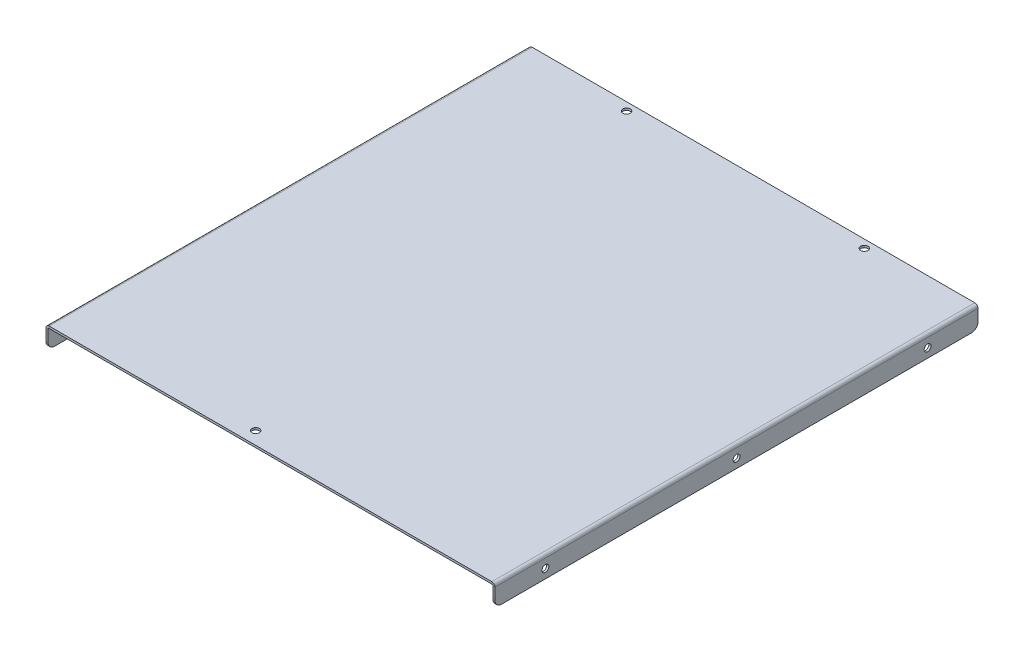
SolidWorks part; units mm, degrees
note: The reader was unsure of these and kept them because the rebuilt part matched: flange length of "Edge-Flange1", "Edge-Flange2".
ref_plane "Front Plane" through (0, 0, 0) normal (0, 0, 1) x (1, 0, 0)
ref_plane "Top Plane" through (0, 0, 0) normal (0, 1, 0) x (1, 0, 0)
ref_plane "Right Plane" through (0, 0, 0) normal (1, 0, 0) x (0, 0, -1)
sketch "Sketch1" plane through (0, 0, 0) normal (0, 1, 0) x (1, 0, 0)
  line L1 (-105.75, 113.75) -> (105.75, 113.75)
  line L2 (-105.75, 113.75) -> (-105.75, -113.75)
  line L3 (-105.75, -113.75) -> (105.75, -113.75)
  line L4 (105.75, 113.75) -> (105.75, -113.75)
  line L5 (-105.75, 113.75) -> (105.75, -113.75) construction
  line L6 (-105.75, -113.75) -> (105.75, 113.75) construction
  point P0 (0, 0)
  dimension "D1" = 211.5
  dimension "D2" = 227.5
base flange "Base-Flange1" sketch "Sketch1" thickness 1 reverse thickness direction no parameters "D1"=8
ref_plane "Plane1" through (105.75, -1, 113.75) normal (0, 0, -1) x (-1, 0, 0)
edge flange "Edge-Flange1" sketch "Sketch9" flange angle 90 flange length 10 flange position material inside bend radius 0.5 thickness 1 relief rectangular parameters "D6"=10
sketch "Sketch9" plane through (105.75, -1, 0) normal (1, 0, 0) x (0, 0, 1)
  line L2 (-113.75, 0) -> (-113.75, 9)
  line L3 (-113.75, 9) -> (113.75, 9)
  line L4 (113.75, 9) -> (113.75, 0)
  line L7 (113.75, 0) -> (-113.75, 0) construction
  line L8 (113.75, 0) -> (-113.75, 0)
bend "EdgeBend1" bend radius 0.5 bend angle 90 parameters "D5"=1
edge flange "Edge-Flange2" sketch "Sketch12" flange angle 90 flange length 10 flange position material inside bend radius 0.5 thickness 1 relief rectangular parameters "D6"=10
sketch "Sketch12" plane through (-105.75, -1, 0) normal (-1, 0, 0) x (0, 0, -1)
  line L2 (-113.75, 0) -> (-113.75, 9)
  line L3 (-113.75, 9) -> (113.75, 9)
  line L4 (113.75, 9) -> (113.75, 0)
  line L7 (113.75, 0) -> (-113.75, 0) construction
  line L8 (113.75, 0) -> (-113.75, 0)
bend "EdgeBend2" bend radius 0.5 bend angle 90 parameters "D5"=2
sketch "Sketch13" plane through (-105.75, 0, 0) normal (-1, 0, 0) x (0, 0, 1)
  line L0 (0, -1.5) -> (0, -10) construction
  line L1 (-113.75, -1.5) -> (113.75, -1.5) construction
  line L2 (-113.75, -10) -> (113.75, -10) construction
  line L3 (-90, -5.75) -> (90, -5.75) construction
  circle A0 centre (0, -5.75) radius 1.6
  circle A1 centre (90, -5.75) radius 1.6
  circle A2 centre (-90, -5.75) radius 1.6
  point P9 (0, -5.75)
  point P10 (0, -5.75)
  dimension "D2" = 3.2
  dimension "D1" = 180
extrude "Cut-Extrude1" cut sketch "Sketch13" against normal through all normal cut yes
fillet "Fillet1" radius 3 4 edges at (105.25, -10, -113.75) (105.25, -10, 113.75) (-105.25, -10, 113.75) (-105.25, -10, -113.75)
sketch "Sketch14" plane through (0, 0, 0) normal (0, 1, 0) x (1, 0, 0)
  circle A0 centre (-56, 109.95) radius 1.75
  circle A1 centre (56, 109.95) radius 1.75
  dimension "D1" = 3.5
extrude "Cut-Extrude2" cut sketch "Sketch14" against normal through all normal cut yes
sketch "Sketch15" plane through (0, 0, 0) normal (0, 1, 0) x (1, 0, 0)
  circle A0 centre (-13, -107.75) radius 1.75
  dimension "D1" = 3.5
extrude "Cut-Extrude3" cut sketch "Sketch15" against normal through all normal cut yes
sketch "Bend-Lines1" [suppressed] plane through (0, 0, 0) normal (0, 1, 0) x (1, 0, 0)
sketch "Bounding-Box1" [suppressed] plane through (0, 0, 0) normal (0, 1, 0) x (1, 0, 0)
sheet metal parameters "Sheet-Metal1" thickness 1 parameters "D1"=8
flat pattern "Flat-Pattern1" [suppressed]
sketch "Bend-Lines2" plane through (0, 0, 0) normal (0, 1, 0) x (1, 0, 0)
sketch3d "Bounding-Box2" [suppressed]
  line L0 (105.75, 115.25, 0) -> (105.75, -115.25, 0) construction
  line L1 (-105.75, 115.25, 0) -> (-105.75, -115.25, 0) construction
  line L2 (105.75, 115.25, 0) -> (-105.75, 115.25, 0) construction
  line L3 (105.75, -115.25, 0) -> (-105.75, -115.25, 0) construction
sheet metal parameters "Sheet-Metal2" thickness 1 parameters "D1"=8
flat pattern "Flat-Pattern1" [suppressed]
sketch "Bend-Lines2" plane through (0, 0, 0) normal (0, 1, 0) x (1, 0, 0)
  line L0 (105.0354, -115.25) -> (105.0354, 115.25) construction
  line L1 (105.0354, -115.25) -> (105.0354, 115.25) construction
sketch3d "Bounding-Box2" [suppressed]
  line L0 (-105.75, 115.25, 0) -> (-105.75, -115.25, 0) construction
  line L1 (114.3208, 115.25, 0) -> (114.3208, -115.25, 0) construction
  line L2 (-105.75, 115.25, 0) -> (114.3208, 115.25, 0) construction
  line L3 (-105.75, -115.25, 0) -> (114.3208, -115.25, 0) construction
bend of the flat pattern "Flatten-<EdgeBend1>1"
sheet metal parameters "Sheet-Metal3" thickness 1 parameters "D1"=8
flat pattern "Flat-Pattern1"
sketch "Bend-Lines2" plane through (0, 0, 0) normal (0, 1, 0) x (1, 0, 0)
  line L0 (105.0354, -113.75) -> (105.0354, 113.75) construction
  line L1 (105.0354, -113.75) -> (105.0354, 113.75) construction
  line L2 (-105.0354, 113.75) -> (-105.0354, -113.75) construction
  line L3 (-105.0354, 113.75) -> (-105.0354, -113.75) construction
sketch3d "Bounding-Box2" [suppressed]
  line L0 (114.3208, -113.75, 0) -> (-114.3208, -113.75, 0) construction
  line L1 (114.3208, 113.75, 0) -> (-114.3208, 113.75, 0) construction
  line L2 (114.3208, -113.75, 0) -> (114.3208, 113.75, 0) construction
  line L3 (-114.3208, -113.75, 0) -> (-114.3208, 113.75, 0) construction
bend of the flat pattern "Flatten-<EdgeBend1>1"
bend of the flat pattern "Flatten-<EdgeBend2>1"
sheet metal parameters "Sheet-Metal4" thickness 1 parameters "D1"=8
flat pattern "Flat-Pattern1"
sketch "Bend-Lines2" plane through (0, 0, 0) normal (0, 1, 0) x (1, 0, 0)
  line L0 (105.0354, -113.75) -> (105.0354, 113.75) construction
  line L1 (105.0354, -113.75) -> (105.0354, 113.75) construction
  line L2 (-105.0354, 113.75) -> (-105.0354, -113.75) construction
  line L3 (-105.0354, 113.75) -> (-105.0354, -113.75) construction
sketch3d "Bounding-Box2" [suppressed]
  line L0 (-114.3208, -113.75, 0) -> (114.3208, -113.75, 0) construction
  line L1 (-114.3208, 113.75, 0) -> (114.3208, 113.75, 0) construction
  line L2 (-114.3208, -113.75, 0) -> (-114.3208, 113.75, 0) construction
  line L3 (114.3208, -113.75, 0) -> (114.3208, 113.75, 0) construction
bend of the flat pattern "Flatten-<EdgeBend1>1"
bend of the flat pattern "Flatten-<EdgeBend2>1"
sheet metal parameters "Sheet-Metal5" thickness 1 parameters "D1"=8
flat pattern "Flat-Pattern1"
sketch "Bend-Lines2" plane through (0, 0, 0) normal (0, 1, 0) x (1, 0, 0)
  line L0 (105.0354, -113.75) -> (105.0354, 113.75) construction
  line L1 (105.0354, -113.75) -> (105.0354, 113.75) construction
  line L2 (-105.0354, 113.75) -> (-105.0354, -113.75) construction
  line L3 (-105.0354, 113.75) -> (-105.0354, -113.75) construction
sketch3d "Bounding-Box2" [suppressed]
  line L0 (-114.3208, -113.75, 0) -> (114.3208, -113.75, 0) construction
  line L1 (-114.3208, 113.75, 0) -> (114.3208, 113.75, 0) construction
  line L2 (-114.3208, -113.75, 0) -> (-114.3208, 113.75, 0) construction
  line L3 (114.3208, -113.75, 0) -> (114.3208, 113.75, 0) construction
bend of the flat pattern "Flatten-<EdgeBend1>1"
bend of the flat pattern "Flatten-<EdgeBend2>1"
sheet metal parameters "Sheet-Metal6" thickness 1 parameters "D1"=8
flat pattern "Flat-Pattern1"
sketch "Bend-Lines2" plane through (0, 0, 0) normal (0, 1, 0) x (1, 0, 0)
  line L0 (105.0354, -113.75) -> (105.0354, 113.75) construction
  line L1 (105.0354, -113.75) -> (105.0354, 113.75) construction
  line L2 (-105.0354, 113.75) -> (-105.0354, -113.75) construction
  line L3 (-105.0354, 113.75) -> (-105.0354, -113.75) construction
sketch3d "Bounding-Box2" [suppressed]
  line L0 (-114.3208, -113.75, 0) -> (114.3208, -113.75, 0) construction
  line L1 (-114.3208, 113.75, 0) -> (114.3208, 113.75, 0) construction
  line L2 (-114.3208, -113.75, 0) -> (-114.3208, 113.75, 0) construction
  line L3 (114.3208, -113.75, 0) -> (114.3208, 113.75, 0) construction
bend of the flat pattern "Flatten-<EdgeBend1>1"
bend of the flat pattern "Flatten-<EdgeBend2>1"
equation "\"l5\"=8"
